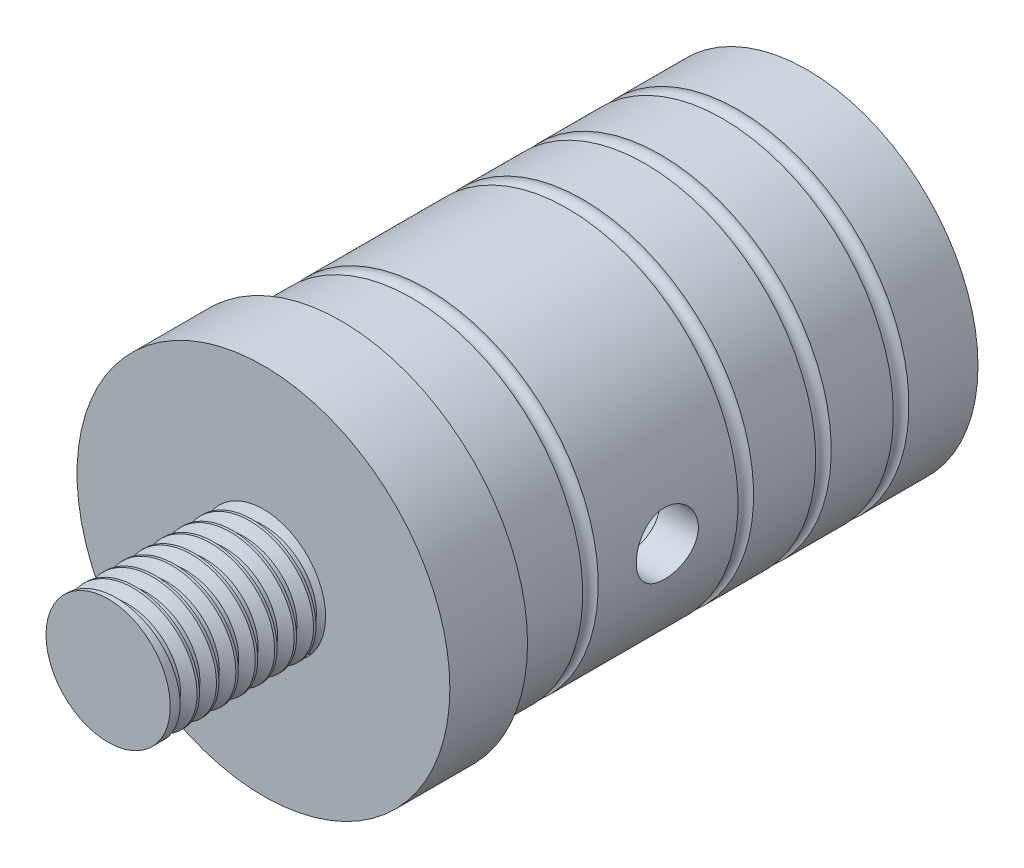
SolidWorks part; units mm, degrees
material "7075-T6 (SN)"
ref_plane "Ön Düzlem" through (0, 0, 0) normal (0, 0, 1) x (1, 0, 0)
ref_plane "Üst Düzlem" through (0, 0, 0) normal (0, 1, 0) x (1, 0, 0)
ref_plane "Sağ Düzlem" through (0, 0, 0) normal (1, 0, 0) x (0, 0, -1)
sketch "Çizim1" plane through (0, 0, 0) normal (0, 0, 1) x (1, 0, 0)
  circle A0 centre (0, 0) radius 8.5
  circle A1 centre (0, 0) radius 11
  dimension "D1" = 17
  dimension "D2" = 22
extrude "Yükseklik-Ekstrüzyon1" add sketch "Çizim1" along normal blind 30
sketch "Çizim2" plane through (0, 0, 30) normal (0, 0, 1) x (1, 0, 0)
  circle A0 centre (0, 0) radius 12
  dimension "D1" = 24
extrude "Yükseklik-Ekstrüzyon2" add sketch "Çizim2" along normal blind 5
sketch "Çizim3" plane through (0, 0, 35) normal (0, 0, 1) x (1, 0, 0)
  circle A0 centre (0, 0) radius 4
  dimension "D1" = 8
extrude "Yükseklik-Ekstrüzyon3" add sketch "Çizim3" along normal blind 10
sketch "Sketch1" plane through (0, 0, 0) normal (1, 0, 0) x (0, 0, -1)
  line L1 (-29.9475, -12) -> (-29.9475, 12)
  line L2 (-24.9475, 11) -> (-24.9475, -11) construction
  line L3 (-14.9475, 11) -> (-14.9475, -11) construction
  line L4 (-9.9475, 11) -> (-9.9475, -11) construction
  line L5 (-4.9475, 11) -> (-4.9475, -11) construction
  line L6 (0.0525, 11) -> (0.0525, -11) construction
  line L9 (0.0525, 0) -> (-29.9475, 0) construction
  line L10 (0.0525, 11) -> (-29.9475, 11)
  circle A0 centre (-24.9475, 11) radius 0.5
  circle A1 centre (-14.9475, 11) radius 0.5
  circle A2 centre (-9.9475, 11) radius 0.5
  circle A3 centre (-4.9475, 11) radius 0.5
  dimension "D6" = 1
  dimension "D7" = 1
  dimension "D8" = 1
  dimension "D9" = 1
  dimension "D1" = 5
  dimension "D2" = 10
  dimension "D3" = 10
  dimension "D4" = 5
revolve "Cut-Revolve1" cut sketch "Sketch1" angle 360 about L9
sketch "Sketch2" plane through (0, 0, 0) normal (1, 0, 0) x (0, 0, -1)
  line L0 (-30, 0) -> (-20, 0) construction
  line L1 (-30, -12) -> (-30, 12) construction
  circle A0 centre (-20, 0) radius 2
  dimension "D2" = 4
  dimension "D1" = 10
extrude "Cut-Extrude1" cut sketch "Sketch2" against normal blind 15 and the other way blind 15
thread "Thread1" pitch 1.25 method cut profile "Thread Profile1" start angle 0, offset 0, length 0, pitch 1.25, diameter 8
ref_plane "Plane1" through (-4, 0, 45) normal (0, -1, 0) x (-1, 0, 0)
sketch "Thread Profile1" plane through (-4, 0, 45) normal (0, -1, 0) x (-1, 0, 0)
  line L0 (0, 0) -> (0, 1.25) construction
  line L11 (0, 0) -> (0, 1.0937)
  line L12 (0, 1.0937) -> (-0.6766, 0.7031)
  line L13 (-0.6766, 0.7031) -> (-0.6766, 0.3906)
  line L15 (-0.6766, 0.3906) -> (0, 0)
  line L17 (-0.6766, 0.5469) -> (0, 0.5469) construction
  point P2 (0, 0)
  dimension "Pitch" = 1.25
  dimension "Profile_Angle" = 60
  dimension "Profile_Land" = 0.3125
  dimension "Profile_Height" = 0.6766
